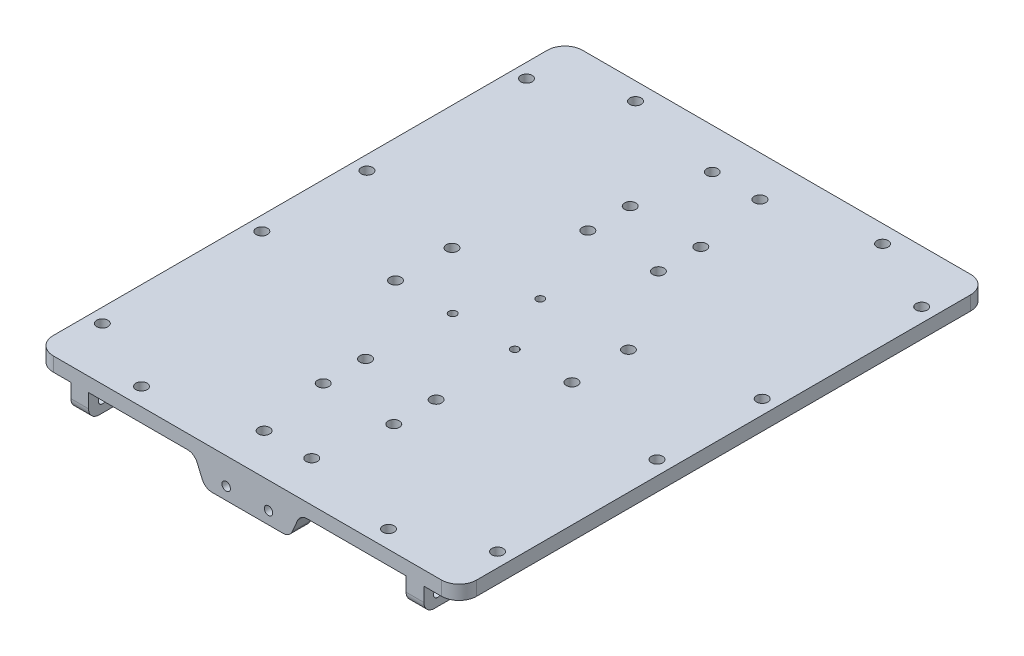
SolidWorks part; units mm, degrees
material "自定义塑料"
ref_plane "前视基准面" through (0, 0, 0) normal (0, 0, 1) x (1, 0, 0)
ref_plane "上视基准面" through (0, 0, 0) normal (0, 1, 0) x (1, 0, 0)
ref_plane "右视基准面" through (0, 0, 0) normal (1, 0, 0) x (0, 0, -1)
sketch "草图1" plane through (0, 0, 0) normal (0, 1, 0) x (1, 0, 0)
  line L0 (0, 0) -> (-20.2314, 0) construction
  line L1 (-60, 75) -> (60, 75)
  line L2 (-60, 75) -> (-60, -75)
  line L3 (-60, -75) -> (60, -75)
  line L4 (60, 75) -> (60, -75)
  line L5 (-60, 75) -> (60, -75) construction
  line L6 (-60, -75) -> (60, 75) construction
  line L7 (0, 0) -> (0, 21.0425) construction
  line L8 (-60, 37.5) -> (-53.3899, 37.5) construction
  circle A0 centre (-56, 60.1) radius 1.6
  circle A1 centre (-56, 14.9) radius 1.6
  circle A2 centre (-10, 43.5) radius 1.6
  circle A3 centre (-10, 31.5) radius 1.6
  circle A4 centre (-56, -14.9) radius 1.6
  circle A5 centre (-10, -31.5) radius 1.6
  circle A6 centre (-10, -43.5) radius 1.6
  circle A7 centre (-56, -60.1) radius 1.6
  circle A8 centre (56, -60.1) radius 1.6
  circle A9 centre (10, -43.5) radius 1.6
  circle A10 centre (10, -31.5) radius 1.6
  circle A11 centre (56, -14.9) radius 1.6
  circle A12 centre (56, 14.9) radius 1.6
  circle A13 centre (10, 31.5) radius 1.6
  circle A14 centre (10, 43.5) radius 1.6
  circle A15 centre (56, 60.1) radius 1.6
  circle A16 centre (0, 8) radius 1.1
  circle A17 centre (8.8, -8) radius 1.1
  circle A18 centre (-8.8, -8) radius 1.1
  circle A19 centre (-25, 8) radius 1.6
  circle A20 centre (25, 8) radius 1.6
  circle A21 centre (25, -8) radius 1.6
  circle A22 centre (-25, -8) radius 1.6
  circle A23 centre (35, 70) radius 1.6
  circle A24 centre (-35, 70) radius 1.6
  circle A25 centre (-35, -70) radius 1.6
  circle A26 centre (35, -70) radius 1.6
  circle A27 centre (-6.75, 63.5) radius 1.6
  circle A28 centre (6.75, 63.5) radius 1.6
  circle A29 centre (6.75, -63.5) radius 1.6
  circle A30 centre (-6.75, -63.5) radius 1.6
  point P0 (0, 0)
  dimension "D4" = 3.2
  dimension "D9" = 2.2
  dimension "D15" = 3.2
  dimension "D16" = 3.2
  dimension "D17" = 70
  dimension "D18" = 140
  dimension "D19" = 3.2
  dimension "D20" = 3.25
  dimension "D21" = 20
  dimension "D1" = 120
  dimension "D2" = 150
  dimension "D3" = 37.5
  dimension "D5" = 45.2
  dimension "D6" = 4
  dimension "D7" = 12
  dimension "D8" = 46
  dimension "D10" = 8
  dimension "D11" = 8
  dimension "D12" = 8.8
  dimension "D13" = 50
  dimension "D14" = 16
extrude "凸台-拉伸1" add sketch "草图1" along normal blind 4
ref_plane "基准面1" through (-50, 0, 0) normal (-1, 0, 0) x (0, 0, 1)
sketch "草图2" plane through (-50, 0, 0) normal (-1, 0, 0) x (0, 0, 1)
  line L0 (45, 0) -> (75, 0)
  line L1 (-75, 0) -> (75, 0) construction
  line L2 (75, 0) -> (75, -7)
  line L4 (57.1244, -7) -> (45, 0)
  line L5 (75, 4) -> (75, 0) construction
  line L6 (0, 31.7776) -> (0, -46.127) construction
  line L9 (-72.6356, 0) -> (-75, 0)
  line L11 (57.1244, -7) -> (75, -7)
  line L14 (-57.1244, -7) -> (-75, -7)
  line L15 (-57.1244, -7) -> (-45, 0)
  line L16 (-75, 0) -> (-75, -7)
  line L17 (-45, 0) -> (-75, 0)
  line L20 (-25, 0) -> (25, 0)
  line L21 (25, 0) -> (17, -7)
  line L23 (17, -7) -> (-17, -7)
  line L24 (-25, 0) -> (-17, -7)
  circle A6 centre (71, -3.5) radius 1.25
  circle A7 centre (-71, -3.5) radius 1.25
  circle A10 centre (65, -3.5) radius 1.25
  circle A11 centre (59, -3.5) radius 1.25
  circle A12 centre (-65, -3.5) radius 1.25
  circle A13 centre (-59, -3.5) radius 1.25
  point P33 (0, -7)
  point P34 (0, 0)
  dimension "D1" = 7
  dimension "D2" = 2.5
  dimension "D6" = 3.5
  dimension "D7" = 4
  dimension "D8" = 3
  dimension "D9" = 34
  dimension "D3" = 90
  dimension "D4" = 30
  dimension "D5" = 30
  dimension "D10" = 50
extrude "凸台-拉伸2" add sketch "草图2" against normal blind 5 contours L4 L11 L2 L0 | L15 L17 L9 L16 L14 A7 | L6 L20 L24 L23 | L20 L6 L23 L21 region at (-50, -3.1761, 62.5609) region at (-50, -3.2778, 10.627) region at (-50, -3.2778, -10.627) region at (-50, -3.1761, -62.5609)
ref_plane "基准面2" through (0, 0, 0) normal (-1, 0, 0) x (0, 0, 1)
mirror "镜向1" about plane through (0, 0, 0) normal (-1, 0, 0) of "凸台-拉伸2"
sketch "草图3" plane through (0, 0, 75) normal (0, 0, 1) x (1, 0, 0)
  line L0 (0, 17.4741) -> (0, -19.202) construction
  line L1 (-15, 0) -> (15, 0)
  line L2 (-45, 0) -> (45, 0) construction
  line L5 (-12, -7) -> (12, -7)
  line L6 (12, -7) -> (15, 0)
  line L7 (-12, -7) -> (-15, 0)
  circle A0 centre (6, -3.5) radius 1.2
  circle A1 centre (-6, -3.5) radius 1.2
  point P10 (0, -7)
  point P11 (0, 0)
  dimension "D5" = 2.4
  dimension "D6" = 12
  dimension "D1" = 30
  dimension "D2" = 24
  dimension "D3" = 7
  dimension "D4" = 3.5
extrude "凸台-拉伸3" add sketch "草图3" against normal blind 5
ref_plane "基准面3" through (0, 0, 0) normal (0, 0, 1) x (1, 0, 0)
mirror "镜向2" about plane through (0, 0, 0) normal (0, 0, 1) of "凸台-拉伸3"
fillet "圆角1" radius 5 4 edges at (-60, 2, -75) (60, 2, -75) (60, 2, 75) (-60, 2, 75)
fillet "圆角3" radius 3 28 edges at (-47.5, 0, 45) (-47.5, -7, 57.1244) (-47.5, -7, 75) (47.5, -7, 75) (47.5, -7, 57.1244) (47.5, 0, 45) (47.5, 0, -45) (-47.5, 0, -45) (47.5, -7, -75) (47.5, -7, -57.1244) (-47.5, -7, -57.1244) (-47.5, -7, -75) (-47.5, -7, 17) (-47.5, 0, 25) (-47.5, 0, -25) (-47.5, -7, -17) (47.5, 0, -25) (47.5, -7, -17) (47.5, -7, 17) (47.5, 0, 25) (-12, -7, -72.5) (-15, 0, -72.5) (12, -7, -72.5) (15, 0, -72.5) (-12, -7, 72.5) (-15, 0, 72.5) (12, -7, 72.5) (15, 0, 72.5)
